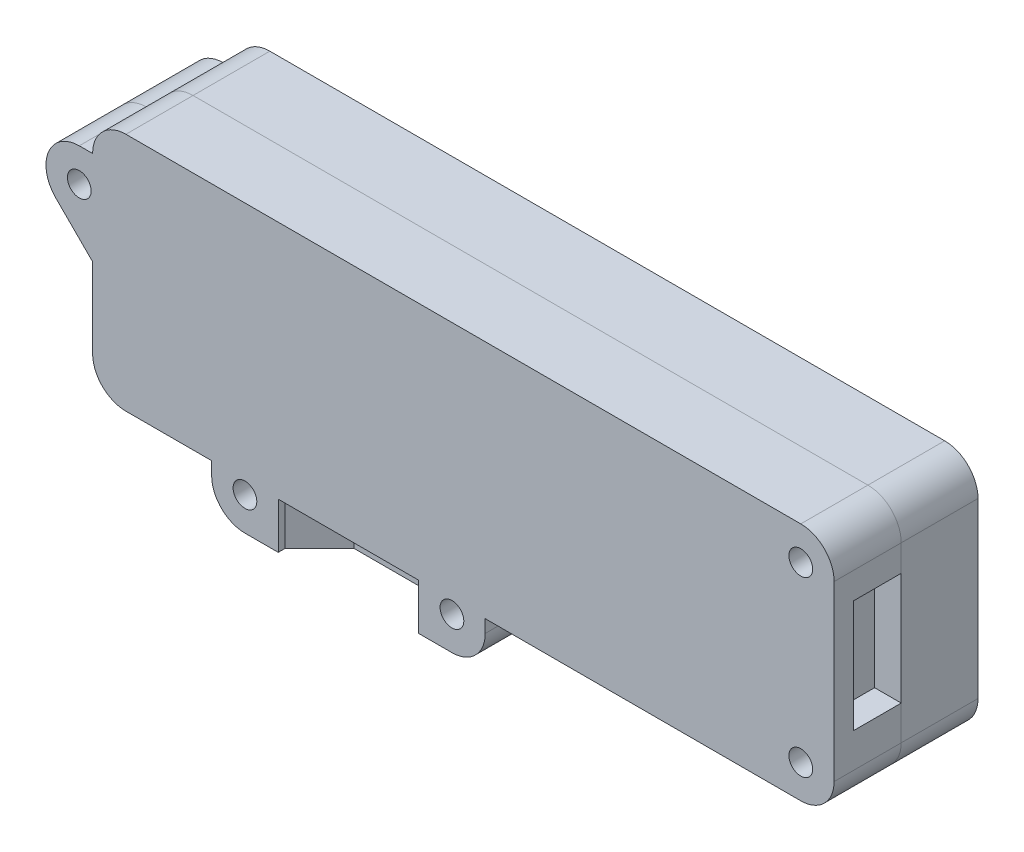
SolidWorks part; units mm, degrees
ref_plane "Front Plane" through (0, 0, 0) normal (0, 0, 1) x (1, 0, 0)
ref_plane "Top Plane" through (0, 0, 0) normal (0, 1, 0) x (1, 0, 0)
ref_plane "Right Plane" through (0, 0, 0) normal (1, 0, 0) x (0, 0, -1)
sketch "Sketch1" plane through (0, 0, 0) normal (0, 0, 1) x (1, 0, 0)
  line L0 (-18.415, 11.43) -> (45.9072, 11.43)
  line L1 (20.32, -10.16) -> (-20.32, -10.16) construction
  line L2 (20.32, -10.16) -> (20.32, 10.16) construction
  line L3 (20.32, 10.16) -> (-20.32, 10.16) construction
  line L4 (-20.32, -10.16) -> (-20.32, 10.16) construction
  line L5 (20.32, -10.16) -> (-20.32, 10.16) construction
  line L6 (20.32, 10.16) -> (-20.32, -10.16) construction
  line L7 (47.8122, 6.5945) -> (13.462, 6.5945) construction
  line L8 (47.8122, 6.5945) -> (47.8122, -6.5945) construction
  line L9 (47.8122, -6.5945) -> (13.462, -6.5945) construction
  line L10 (13.462, 6.5945) -> (13.462, -6.5945) construction
  line L11 (-20.32, -10.16) -> (47.8122, -10.16) construction
  line L12 (-20.32, -10.16) -> (-20.32, 10.16) construction
  line L13 (-20.32, 10.16) -> (47.8122, 10.16) construction
  line L14 (47.8122, -10.16) -> (47.8122, 10.16) construction
  line L15 (49.0822, -8.255) -> (49.0822, 8.255)
  line L16 (-18.415, -11.43) -> (45.9072, -11.43)
  line L17 (-21.59, -8.255) -> (-21.59, 8.255)
  line L18 (-21.59, -11.43) -> (-21.59, 11.43) construction
  line L19 (-21.59, 11.43) -> (49.0822, 11.43) construction
  line L20 (-21.59, -11.43) -> (49.0822, -11.43) construction
  line L21 (49.0822, -11.43) -> (49.0822, 11.43) construction
  arc A0 (-21.59, 8.255) -> (-18.415, 11.43) centre (-18.415, 8.255) cw
  arc A1 (-18.415, -11.43) -> (-21.59, -8.255) centre (-18.415, -8.255) cw
  arc A2 (45.9072, -11.43) -> (49.0822, -8.255) centre (45.9072, -8.255) ccw
  arc A3 (45.9072, 11.43) -> (49.0822, 8.255) centre (45.9072, 8.255) cw
  point P0 (0, 0)
  dimension "D2" = 3.175
  dimension "D3" = 3.175
  dimension "D4" = 3.175
  dimension "D5" = 3.175
  dimension "D1" = 1.27
extrude "Boss-Extrude1" add sketch "Sketch1" against normal blind 13.716 from offset 0.762 contours A2 L15 A3 L0 A0 L17 A1 L16
sketch "Sketch2" plane through (49.0822, 0, 0) normal (1, 0, 0) x (0, 0, -1)
  line L0 (1.8501, 0.3831) -> (4.8754, 0.3831) construction
  line L1 (1.8501, 0.6303) -> (1.8501, 0.1358) construction
  line L2 (4.8754, 4.611) -> (4.8754, -2.4701) construction
  line L3 (4.5525, 5.2318) -> (3.002, 5.2318) construction
  line L4 (1.0881, -4.9737) -> (5.6374, -4.9737)
  line L5 (1.0881, -4.9737) -> (1.0881, 5.7398)
  line L6 (1.0881, 5.7398) -> (5.6374, 5.7398)
  line L7 (5.6374, -4.9737) -> (5.6374, 5.7398)
  line L8 (1.0881, -4.9737) -> (5.6374, 5.7398) construction
  line L9 (1.0881, 5.7398) -> (5.6374, -4.9737) construction
  point P6 (3.3627, 0.3831)
  dimension "D1" = 0.762
  dimension "D2" = 0.508
extrude "Cut-Extrude1" cut sketch "Sketch2" against normal blind 2.54
sketch "Sketch3" plane through (0, -11.43, 0) normal (0, -1, 0) x (1, 0, 0)
  line L0 (9.483, -8.953) -> (-3.895, -8.953)
  line L1 (8.594, -4.064) -> (-3.006, -4.064) construction
  line L2 (8.594, -4.064) -> (8.594, -8.064) construction
  line L3 (8.594, -8.064) -> (-3.006, -8.064) construction
  line L4 (-3.006, -4.064) -> (-3.006, -8.064) construction
  line L5 (8.594, -4.064) -> (-3.006, -8.064) construction
  line L6 (8.594, -8.064) -> (-3.006, -4.064) construction
  line L7 (-3.895, -3.175) -> (-3.895, -8.953)
  line L8 (9.483, -3.175) -> (-3.895, -3.175)
  line L9 (9.483, -3.175) -> (9.483, -8.953)
  line L10 (5.552, -4.556) -> (5.552, -7.572)
  line L11 (5.044, -5.064) -> (0.544, -5.064) construction
  line L12 (5.044, -5.064) -> (5.044, -7.064) construction
  line L13 (5.044, -7.064) -> (0.544, -7.064) construction
  line L14 (0.544, -5.064) -> (0.544, -7.064) construction
  line L15 (5.044, -5.064) -> (0.544, -7.064) construction
  line L16 (5.044, -7.064) -> (0.544, -5.064) construction
  line L17 (5.552, -7.572) -> (0.036, -7.572)
  line L18 (0.036, -4.556) -> (0.036, -7.572)
  line L19 (5.552, -4.556) -> (0.036, -4.556)
  point P0 (2.794, -6.064)
  point P11 (2.794, -6.064)
  dimension "D1" = 0.889
  dimension "D2" = 0.508
extrude "Boss-Extrude2" add sketch "Sketch3" along normal offset from surface (4.3946 mm away) 1.016 offset beyond the face yes
sketch "Sketch6" plane through (0, 0, -12.954) normal (0, 0, -1) x (-1, 0, 0)
  line L0 (18.415, -11.43) -> (-45.9072, -11.43) construction
  line L1 (21.59, 0) -> (-49.0822, 0) construction
  line L2 (21.59, -8.255) -> (21.59, 8.255) construction
  line L3 (-49.0822, -8.255) -> (-49.0822, 8.255) construction
  line L4 (22.86, 8.255) -> (21.59, 8.255)
  line L5 (21.59, 8.255) -> (21.59, 1.905)
  line L6 (21.59, 1.905) -> (22.86, 1.905) construction
  line L7 (3.895, -15.8246) -> (3.895, -11.43) construction
  line L8 (7.07, -15.8246) -> (3.895, -15.8246)
  line L9 (25.1051, 2.8349) -> (21.59, -0.6801)
  line L10 (10.245, -12.6496) -> (10.245, -11.43)
  line L11 (10.245, -11.43) -> (3.895, -11.43)
  line L12 (3.895, -11.43) -> (3.895, -15.8246)
  line L13 (21.59, -8.255) -> (21.59, 8.255) construction
  line L14 (21.59, -0.6801) -> (21.59, 1.905)
  line L15 (-2.794, -15.8246) -> (-2.794, -11.43) construction
  line L16 (3.895, -15.8246) -> (-9.483, -15.8246) construction
  line L17 (18.415, -11.43) -> (-45.9072, -11.43) construction
  line L18 (-9.483, -11.43) -> (-9.483, -15.8246)
  line L19 (-15.833, -11.43) -> (-9.483, -11.43)
  line L20 (-15.833, -12.6496) -> (-15.833, -11.43)
  line L21 (-12.658, -15.8246) -> (-9.483, -15.8246)
  arc A0 (7.07, -15.8246) -> (10.245, -12.6496) centre (7.07, -12.6496) ccw
  arc A1 (21.59, 8.255) -> (18.415, 11.43) centre (18.415, 8.255) ccw construction
  arc A2 (5.3627, -9.9727) -> (3.895, -12.6496) centre (7.07, -12.6496) ccw construction
  arc A3 (25.1051, 2.8349) -> (22.86, 8.255) centre (22.86, 5.08) ccw
  arc A4 (-10.9507, -9.9727) -> (-9.483, -12.6496) centre (-12.658, -12.6496) cw construction
  arc A5 (-12.658, -15.8246) -> (-15.833, -12.6496) centre (-12.658, -12.6496) cw
  dimension "D1" = 6.35
  dimension "D2" = 45
  dimension "D3" = 6.35
  dimension "D4" = 1.27
  dimension "D5" = 3.175
extrude "Boss-Extrude3" add sketch "Sketch6" against normal through all
ref_plane "Plane1" through (0, 0, -6.096) normal (0, 0, 1) x (1, 0, 0)
hole_wizard "CSK for #4 Flat Head Machine Screw (100)1" positions "Sketch8" profile "Sketch7" countersink size "#4" standard "ANSI Inch"
sketch "Sketch8" plane through (0, 0, -12.954) normal (0, 0, -1) x (-1, 0, 0)
  point P0 (-45.9072, -8.255)
  point P3 (-45.9072, 8.255)
  point P6 (7.07, -12.6496)
  point P9 (22.86, 5.08)
  point P15 (-12.658, -12.6496)
sketch "Sketch7" plane through (45.9072, -8.255, -12.954) normal (1, 0, 0) x (0, 1, 0)
  line L0 (0, 0) -> (0, 8.2018)
  line L1 (0, 8.2018) -> (1.4732, 7.3166)
  line L2 (1.4732, 7.3166) -> (1.4732, 1.1616)
  line L3 (1.4732, 1.1616) -> (2.8575, 0)
  line L5 (2.8575, 0) -> (0, 0)
  line L6 (-1.4732, 1.1616) -> (-2.8575, 0) construction
  line L10 (0, 8.2018) -> (-1.4732, 7.3166) construction
  line L11 (0, -6.35) -> (0, 107.95) construction
  dimension "Hole Dia." = 2.9464
  dimension "Hole Depth" = 7.3166
  dimension "Near C'Sink Dia." = 5.715
  dimension "Near C'Sink Angle" = 100
  dimension "Drill Angle" = 118
ref_plane "Plane2" through (0, 0, -5.6374) normal (0, 0, 1) x (1, 0, 0)
hole_wizard "Tap Drill for #4-40 Tap1" positions "Sketch10" profile "Sketch9" hole size "#4-40" standard "ANSI Inch" end condition through all
sketch "Sketch10" plane through (0, 0, -5.6374) normal (0, 0, -1) x (-1, 0, 0)
  point P0 (-45.9072, 8.255)
  point P3 (-45.9072, -8.255)
  point P6 (22.86, 5.08)
  point P9 (7.07, -12.6496)
  point P12 (-12.658, -12.6496)
sketch "Sketch9" plane through (45.9072, 8.255, -5.6374) normal (1, 0, 0) x (0, 1, 0)
  line L0 (0, 0) -> (0, 6.3994)
  line L1 (0, 6.3994) -> (1.1303, 6.3994)
  line L2 (1.1303, 6.3994) -> (1.1303, 0)
  line L5 (1.1303, 0) -> (0, 0)
  line L11 (0, -6.35) -> (0, 107.95) construction
  dimension "Thru Hole Dia." = 2.2606
  dimension "Thru Hole Depth" = 6.3994
chamfer "Chamfer2" distance 3.302 angle 45 6 edges at (2.794, -11.43, -8.953) (-3.895, -13.6273, -8.953) (-3.895, -13.6273, -3.175) (2.794, -11.43, -3.175) (9.483, -13.6273, -3.175) (9.483, -13.6273, -8.953)
split "Split1" bodies to split 109 resulting bodies 107 108 split by face at (47.8122, 0.3831, -5.6374)
